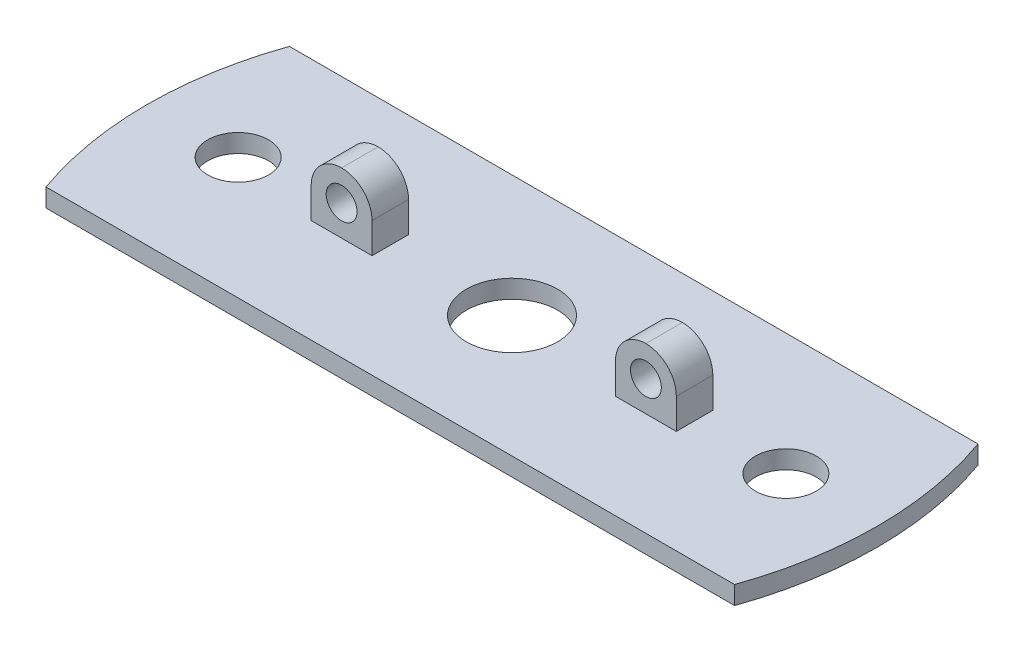
SolidWorks part; units mm, degrees
ref_plane "Piano frontale" through (0, 0, 0) normal (0, 0, 1) x (1, 0, 0)
ref_plane "Piano superiore" through (0, 0, 0) normal (0, 1, 0) x (1, 0, 0)
ref_plane "Piano destro" through (0, 0, 0) normal (1, 0, 0) x (0, 0, -1)
sketch "Schizzo1" plane through (0, 0, 0) normal (0, 1, 0) x (1, 0, 0)
  line L0 (-55, 0) -> (55, 0) construction
  line L1 (0, -55) -> (0, 55) construction
  line L2 (-56.5685, 20) -> (56.5685, 20)
  line L3 (-56.5685, -20) -> (56.5685, -20)
  arc A0 (-56.5685, 20) -> (-56.5685, -20) centre (0, 0) ccw
  circle A1 centre (45, 0) radius 5
  circle A2 centre (-45, 0) radius 5
  arc A3 (56.5685, -20) -> (56.5685, 20) centre (0, 0) ccw
  circle A4 centre (0, 0) radius 7.5
  dimension "D1" = 120
  dimension "D2" = 10
  dimension "D3" = 10
  dimension "D8" = 15
  dimension "D4" = 45
  dimension "D5" = 45
  dimension "D6" = 20
  dimension "D7" = 40
extrude "Estrusione-Estrusione1" add sketch "Schizzo1" along normal blind 3
sketch "Schizzo3" plane through (0, 3, 0) normal (0, 1, 0) x (1, 0, 0)
  line L0 (-1.65, 0) -> (1.65, 0) construction
  line L1 (-30, 3) -> (-20, 3)
  line L2 (-30, 3) -> (-30, -3)
  line L3 (-30, -3) -> (-20, -3)
  line L4 (-20, 3) -> (-20, -3)
  line L5 (-30, 3) -> (-20, -3) construction
  line L6 (-30, -3) -> (-20, 3) construction
  line L7 (0, -1.65) -> (0, 1.65) construction
  point P0 (-25, 0)
  dimension "D1" = 10
  dimension "D2" = 6
  dimension "D3" = 25
extrude "Estrusione-Estrusione2" add sketch "Schizzo3" along normal blind 10
sketch "Schizzo4" plane through (0, 0, 3) normal (0, 0, 1) x (1, 0, 0)
  line L0 (-30, 13) -> (-20, 13) construction
  line L1 (-30, 13) -> (-30, 3) construction
  circle A0 centre (-25, 8) radius 2.5347
  dimension "D1" = 5
  dimension "D2" = 5
extrude "Taglio-Estrusione1" cut sketch "Schizzo4" against normal blind 9
fillet "Raccordo1" radius 5 2 edges at (-20, 13, 0) (-30, 13, 0)
mirror "Specchia1" about plane through (0, 0, 0) normal (1, 0, 0) of "Raccordo1", "Taglio-Estrusione1", "Estrusione-Estrusione2"
